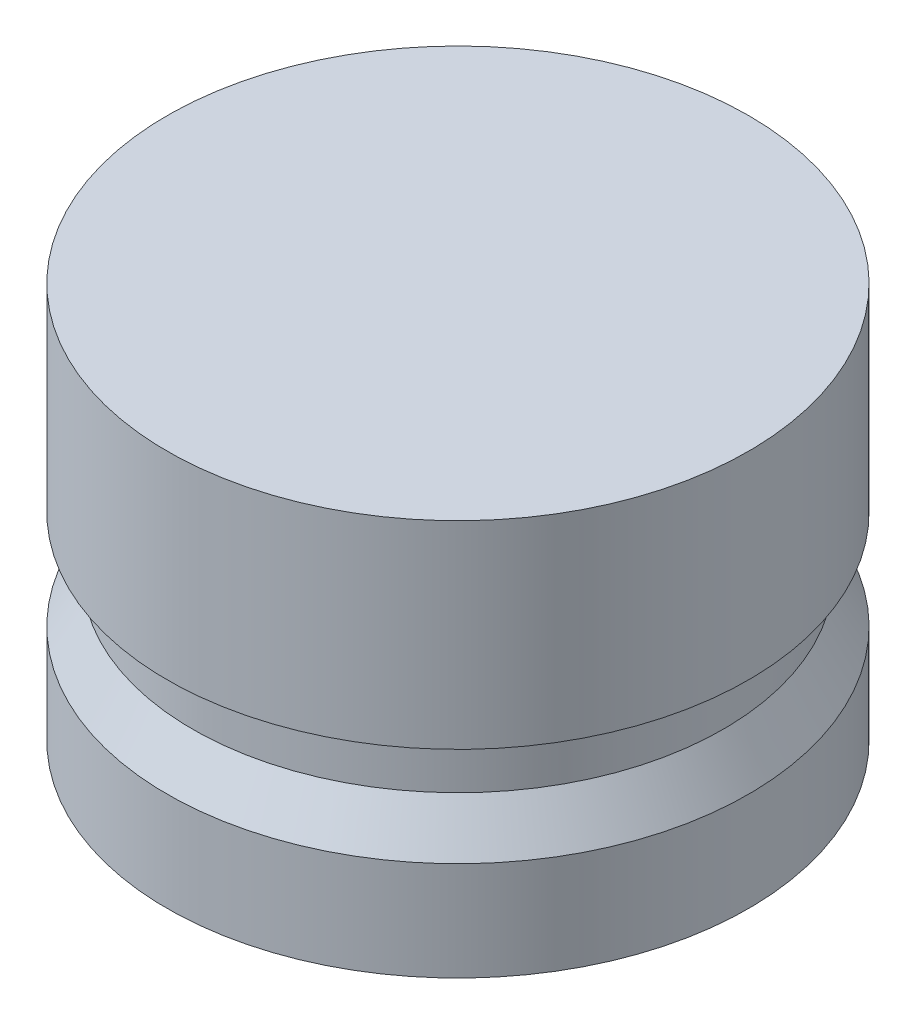
SolidWorks part; units mm, degrees
ref_plane "Front Plane" through (0, 0, 0) normal (0, 0, 1) x (1, 0, 0)
ref_plane "Top Plane" through (0, 0, 0) normal (0, 1, 0) x (1, 0, 0)
ref_plane "Right Plane" through (0, 0, 0) normal (1, 0, 0) x (0, 0, -1)
sketch "Sketch1" plane through (0, 0, 0) normal (0, 0, 1) x (1, 0, 0)
  line L0 (0, 0) -> (0, 12.7) construction
  line L1 (0, 0) -> (-9.3218, 0)
  line L2 (-9.3218, 0) -> (-9.3218, 3.175)
  line L4 (-8.509, 4.572) -> (-8.509, 6.35)
  line L5 (-8.509, 6.35) -> (-9.3218, 6.35)
  line L6 (-9.3218, 6.35) -> (-9.3218, 12.7)
  line L7 (-9.3218, 12.7) -> (0, 12.7)
  line L8 (-9.525, 16.6801) -> (-9.525, -9.6051) construction
  line L9 (0, 0) -> (0, 12.7)
  line L10 (-8.509, 4.572) -> (-9.3218, 3.175)
  dimension "D1" = 12.7
  dimension "D2" = 9.3218
  dimension "D3" = 1.778
  dimension "D4" = 3.175
  dimension "D5" = 9.525
  dimension "D6" = 8.509
  dimension "D7" = 6.35
revolve "Revolve1" add sketch "Sketch1" angle 360 about L9
